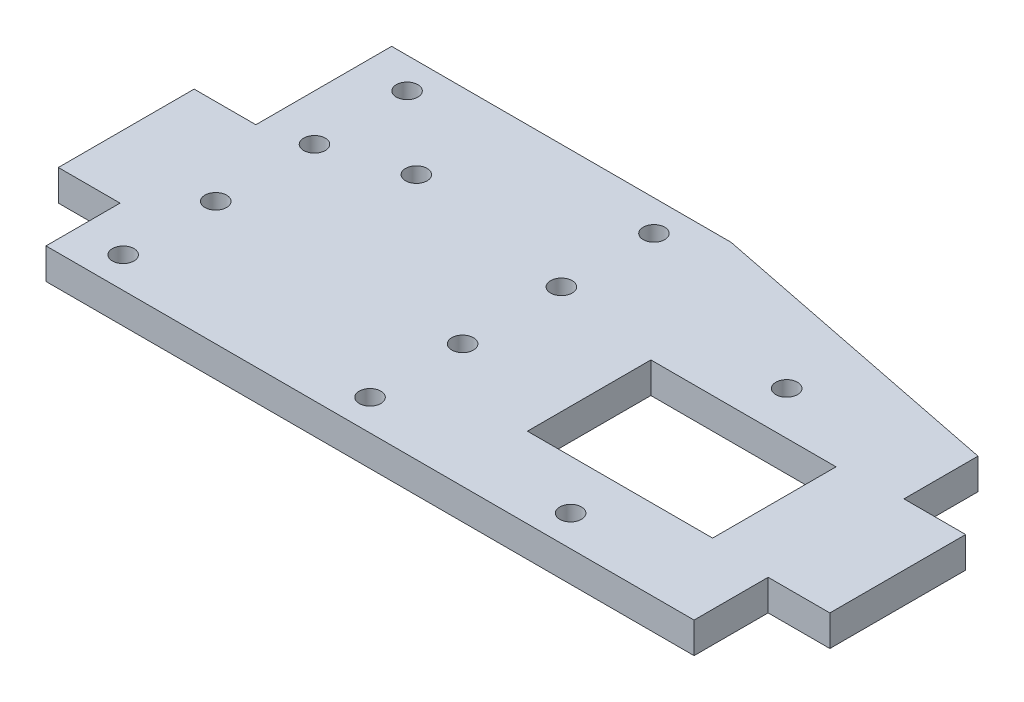
SolidWorks part; units mm, degrees
ref_plane "Front Plane" through (0, 0, 0) normal (0, 0, 1) x (1, 0, 0)
ref_plane "Top Plane" through (0, 0, 0) normal (0, 1, 0) x (1, 0, 0)
ref_plane "Right Plane" through (0, 0, 0) normal (1, 0, 0) x (0, 0, -1)
sketch "Sketch2" plane through (0, 0, 0) normal (0, 1, 0) x (1, 0, 0)
  line L0 (0, 0) -> (0, 8) construction
  line L1 (-27.5, 28) -> (27.5, 28)
  line L2 (-27.5, 28) -> (-27.5, -28)
  line L3 (-27.5, -28) -> (27.5, -28)
  line L4 (27.5, 28) -> (27.5, -28)
  line L5 (-27.5, 28) -> (27.5, -28) construction
  line L6 (-27.5, -28) -> (27.5, 28) construction
  line L7 (0, 8) -> (-20, 8) construction
  line L8 (-20, 8) -> (-20, 23) construction
  line L9 (-55, 0) -> (55, 0) construction
  circle A0 centre (-20, 8) radius 1.75
  circle A1 centre (-20, 23) radius 1.75
  circle A2 centre (20, 8) radius 1.75
  circle A3 centre (20, 23) radius 1.75
  circle A4 centre (20, -8) radius 1.75
  circle A5 centre (20, -23) radius 1.75
  circle A6 centre (-20, -8) radius 1.75
  circle A7 centre (-20, -23) radius 1.75
  point P0 (0, 0)
  dimension "D6" = 3.5
  dimension "D7" = 3.5
  dimension "D1" = 56
  dimension "D2" = 55
  dimension "D3" = 8
  dimension "D4" = 20
  dimension "D5" = 15
extrude "Boss-Extrude1" add sketch "Sketch2" along normal blind 5
sketch "Sketch3" plane through (0, 5, 0) normal (0, 1, 0) x (1, 0, 0)
  line L0 (27.5, 28) -> (27.5, -28)
  line L4 (87.5, -5) -> (52.5, -5) construction
  line L11 (37.5, 5) -> (67.5, 5)
  line L16 (27.5, -28) -> (77.5, -28)
  line L17 (77.5, -28) -> (77.5, -16)
  line L18 (77.5, -16) -> (87.5, -16)
  line L19 (87.5, -16) -> (87.5, 6)
  line L20 (87.5, 6) -> (77.5, 6)
  line L21 (77.5, 6) -> (77.5, 18)
  line L22 (77.5, 18) -> (27.5, 28)
  line L23 (37.5, 5) -> (37.5, -15)
  line L24 (37.5, -15) -> (67.5, -15)
  line L25 (67.5, 5) -> (67.5, -15)
  line L26 (37.5, 5) -> (67.5, -15) construction
  line L27 (37.5, -15) -> (67.5, 5) construction
  dimension "D6" = 10
  dimension "D1" = 50
  dimension "D2" = 12
  dimension "D3" = 35
  dimension "D4" = 20
  dimension "D5" = 30
  dimension "D7" = 22
  dimension "D8" = 10
extrude "Boss-Extrude2" add sketch "Sketch3" against normal up to surface (5 mm away) up to face at (0, 0, 0)
sketch "Sketch5" plane through (0, 5, 0) normal (0, 1, 0) x (1, 0, 0)
  line L0 (-27.5, 0) -> (-27.5, 6) construction
  line L1 (-27.5, 28) -> (-27.5, -28) construction
  line L3 (-27.5, 6) -> (-37.5, 6)
  line L4 (-27.5, 6) -> (-27.5, -16)
  line L5 (-27.5, -16) -> (-37.5, -16)
  line L6 (-37.5, 6) -> (-37.5, -16)
  dimension "D1" = 6
  dimension "D2" = 22
  dimension "D3" = 10
extrude "Boss-Extrude3" add sketch "Sketch5" against normal blind 5
sketch "Sketch6" plane through (0, 5, 0) normal (0, 1, 0) x (1, 0, 0)
  line L0 (-27.5, 6) -> (-27.5, 12) construction
  line L1 (-27.5, 28) -> (-27.5, 6) construction
  line L2 (-27.5, 12) -> (-7.5, 12) construction
  line L3 (-7.5, 12) -> (52.5, 12) construction
  line L4 (20, -23) -> (52.5, -23) construction
  circle A0 centre (-7.5, 12) radius 1.75
  circle A1 centre (52.5, 12) radius 1.75
  circle A4 centre (52.5, -23) radius 1.75
  dimension "D4" = 3.5
  dimension "D5" = 3.5
  dimension "D6" = 3.5
  dimension "D1" = 6
  dimension "D2" = 20
  dimension "D3" = 60
extrude "Cut-Extrude1" cut sketch "Sketch6" against normal blind 5
